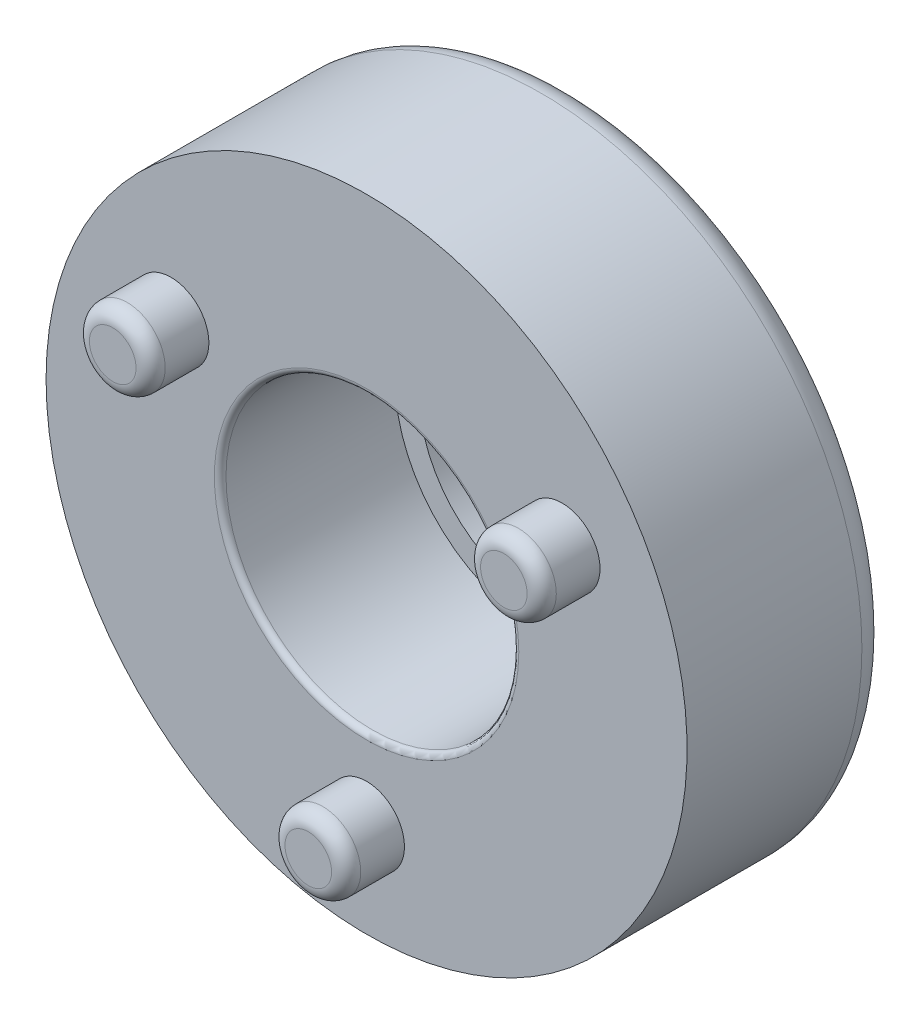
SolidWorks part; units mm, degrees
ref_plane "Front Plane" through (0, 0, 0) normal (0, 0, 1) x (1, 0, 0)
ref_plane "Top Plane" through (0, 0, 0) normal (0, 1, 0) x (1, 0, 0)
ref_plane "Right Plane" through (0, 0, 0) normal (1, 0, 0) x (0, 0, -1)
sketch "Sketch1" plane through (0, 0, 0) normal (0, 0, 1) x (1, 0, 0)
  line L0 (0, 0) -> (0, -7.75) construction
  circle A0 centre (0, 0) radius 4.2
  circle A1 centre (0, 0) radius 26
  circle A2 centre (0, -7.75) radius 1.275 construction
  circle A3 centre (-6.7117, 3.875) radius 1.275 construction
  circle A4 centre (6.7117, 3.875) radius 1.275 construction
  point P12 (0, 0)
  dimension "D3" = 8.4
  dimension "D4" = 2.55
  dimension "D5" = 52
  dimension "D2" = 7.75
  dimension "D1" = 3
extrude "Boss-Extrude1" add sketch "Sketch1" along normal blind 7
sketch "Sketch2" plane through (0, 0, 7) normal (0, 0, 1) x (1, 0, 0)
  circle A0 centre (0, 0) radius 5.025
  circle A1 centre (0, 0) radius 12
  circle A2 centre (0, 0) radius 24.5
  circle M3 centre (0, 0) radius 4.2
  dimension "D1" = 10.05
  dimension "D2" = 24
  dimension "D3" = 49
extrude "Cut-Extrude1" cut sketch "Sketch2" against normal blind 6 contours A2 A1 | A0 M3 region at (-4.8829, 0, 7) region at (-23.807, 0, 7)
fillet "Fillet1" radius 0.2 1 edges at (5.025, 0, 7)
fillet "Fillet2" radius 1 1 edges at (26, 0, 0)
fillet "Fillet3" radius 1 3 edges at (24.5, 0, 1) (12, 0, 1) (12, 0, 7)
sketch "Sketch3" plane through (0, 0, 0) normal (0, 0, 1) x (1, 0, 0)
  circle A2 centre (0, 0) radius 29.9459
  circle A3 centre (0, 0) radius 11 construction
  circle A4 centre (0, 0) radius 11
extrude "Cut-Extrude3" cut sketch "Sketch3" along normal blind 30
sketch "Sketch4" plane through (0, 0, 7) normal (0, 0, 1) x (1, 0, 0)
  circle A0 centre (-6.7117, 3.875) radius 1.3
  circle A1 centre (6.7117, 3.875) radius 1.3
  circle A2 centre (0, -7.75) radius 1.3
  dimension "D1" = 2.6
extrude "Boss-Extrude2" add sketch "Sketch4" along normal blind 2
fillet "Fillet4" radius 1 1 edges at (11, 0, 0)
fillet "Fillet5" radius 0.5 3 edges at (8.0117, 3.875, 9) (1.3, -7.75, 9) (-5.4117, 3.875, 9)
